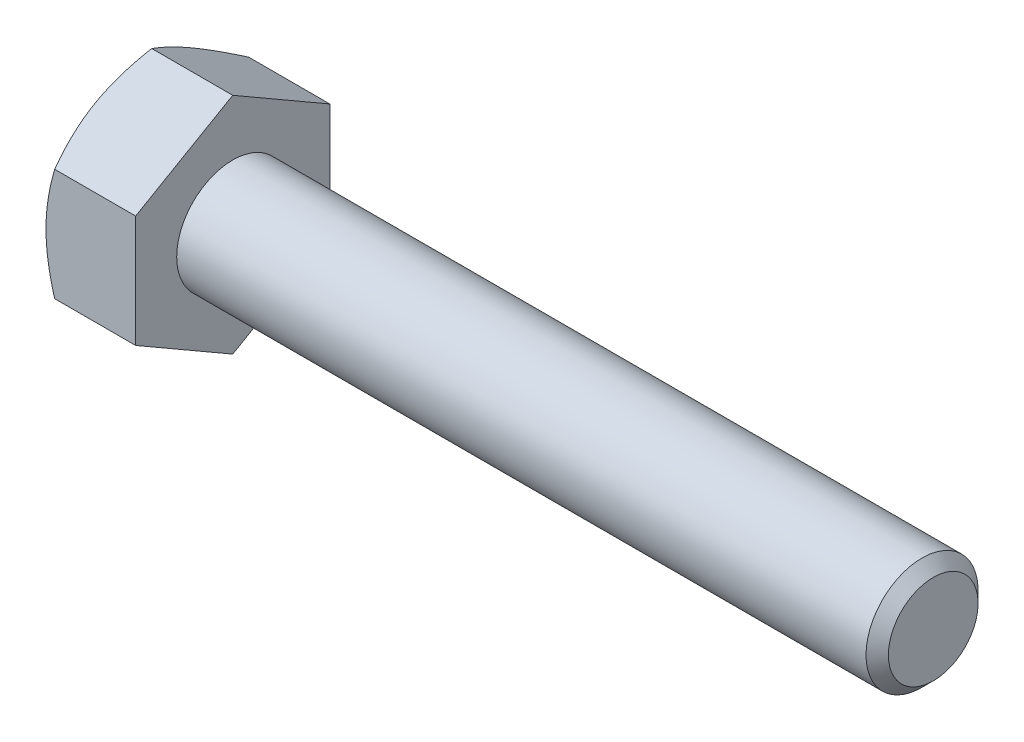
SolidWorks part; units mm, degrees
ref_plane "Front Plane" through (0, 0, 0) normal (0, 0, 1) x (1, 0, 0)
ref_plane "Top Plane" through (0, 0, 0) normal (0, 1, 0) x (1, 0, 0)
ref_plane "Right Plane" through (0, 0, 0) normal (1, 0, 0) x (0, 0, -1)
sketch "Sketch1" plane through (0, 0, 0) normal (1, 0, 0) x (0, 0, -1)
  line L1 (20.7846, -12) -> (20.7846, 12)
  line L2 (20.7846, 12) -> (0, 24)
  line L3 (0, 24) -> (-20.7846, 12)
  line L4 (-20.7846, 12) -> (-20.7846, -12)
  line L5 (-20.7846, -12) -> (0, -24)
  line L6 (0, -24) -> (20.7846, -12)
  circle A0 centre (0, 0) radius 20.7846 construction
  circle A1 centre (0, 0) radius 12
  dimension "D1" = 24
extrude "Boss-Extrude2" add sketch "Sketch1" along normal blind 19.2 contours A1 | L5 L6 L1 L2 L3 L4 A1 region at (0, -17.4501, -10.0748) region at (0, 0, 0)
extrude "Boss-Extrude3" add sketch "Sketch1<5>" along normal blind 169.2 contours A1 region at (0, 0, 0)
sketch "Sketch1<5>" plane through (0, 0, 0) normal (1, 0, 0) x (0, 0, -1) same geometry as "Sketch1"
cosmetic thread "Cosmetic Thread1" parameters "D1"=60, "D2"=23
sketch "Sketch2" plane through (0, 0, 0) normal (-1, 0, 0) x (0, 0, 1)
  circle A0 centre (0, 0) radius 20.7846
extrude "Cut-Extrude1" cut sketch "Sketch2" against normal blind 19.2 draft 60 flip side to cut
chamfer "Chamfer1" distance 2.4 angle 45 1 edges at (169.2, 0, -12)
